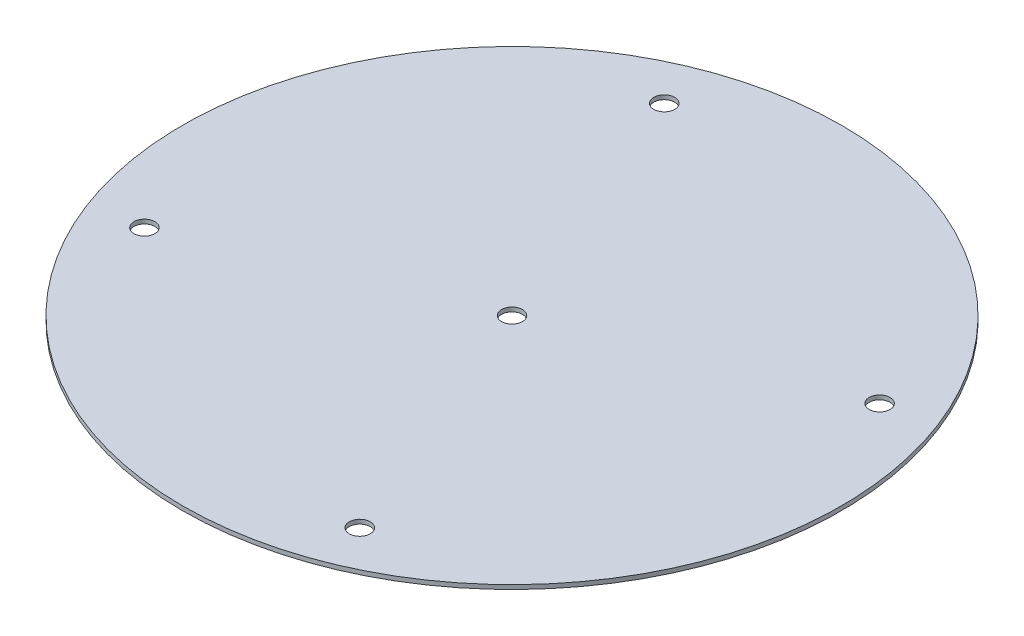
SolidWorks part; units mm, degrees
material "6061-T6 (SS)"
ref_plane "Front Plane" through (0, 0, 0) normal (0, 0, 1) x (1, 0, 0)
ref_plane "Top Plane" through (0, 0, 0) normal (0, 1, 0) x (1, 0, 0)
ref_plane "Right Plane" through (0, 0, 0) normal (1, 0, 0) x (0, 0, -1)
sketch "Sketch2" plane through (0, 0, 0) normal (1, 0, 0) x (0, 0, -1)
  line L0 (0, 0) -> (-77.55, 0)
  line L1 (-77.55, 0) -> (-77.55, 1)
  line L2 (-77.55, 1) -> (0, 1)
  line L5 (0, 1) -> (0, 0)
  dimension "D1" = 77.55
  dimension "D2" = 1
ref_axis "Axis1" through (0, -0.05, 0) along (0, 1, 0)
revolve "Revolve1" add sketch "Sketch2" angle 360 about axis through (0, -0.05, 0) along (0, 1, 0)
hole_wizard "#10 (0.1935) Diameter Hole1" positions "Sketch6" profile "Sketch7" hole size "#10" standard "ANSI Inch" end condition through all
sketch "Sketch6" plane through (0, 1, 0) normal (0, 1, 0) x (1, 0, 0)
  line L0 (0, 0) -> (-53.438, 129.0108) construction
  line L2 (0, 0) -> (0, 109.0908) construction
  point P0 (-25.3336, 61.1608)
  dimension "D1" = 22.5
  dimension "D2" = 66.2
sketch "Sketch7" plane through (-25.3336, 1, -61.1608) normal (1, 0, 0) x (0, 0, 1)
  line L0 (0, 0) -> (0, 1)
  line L1 (0, 1) -> (2.4574, 1)
  line L2 (2.4574, 1) -> (2.4574, 0)
  line L5 (2.4574, 0) -> (0, 0)
  line L11 (0, -6.35) -> (0, 107.95) construction
  dimension "Thru Hole Dia." = 4.9149
  dimension "Thru Hole Depth" = 1
pattern_circular "CirPattern3" count 4 over 360 about axis through (0, -0.05, 0) along (0, 1, 0) of "#10 (0.1935) Diameter Hole1"
hole_wizard "#10 (0.1935) Diameter Hole2" positions "Sketch8" profile "Sketch9" hole size "#10" standard "ANSI Inch" end condition through all
sketch "Sketch8" plane through (0, 1, 0) normal (0, 1, 0) x (1, 0, 0)
  line L0 (0, 0) -> (106.3094, -1.7118) construction
  point P7 (0, 0)
sketch "Sketch9" plane through (0, 1, 0) normal (1, 0, 0) x (0, 0, 1)
  line L0 (0, 0) -> (0, 1)
  line L1 (0, 1) -> (2.4574, 1)
  line L2 (2.4574, 1) -> (2.4574, 0)
  line L5 (2.4574, 0) -> (0, 0)
  line L11 (0, -6.35) -> (0, 107.95) construction
  dimension "Thru Hole Dia." = 4.9149
  dimension "Thru Hole Depth" = 1
equation "\"TubeDiameter\" = 6.500in"
equation "\"D1@Sketch2\"=\"TubeDiameter\"/2-5mm"
equation "\"D2@Sketch6\"=66.2"
